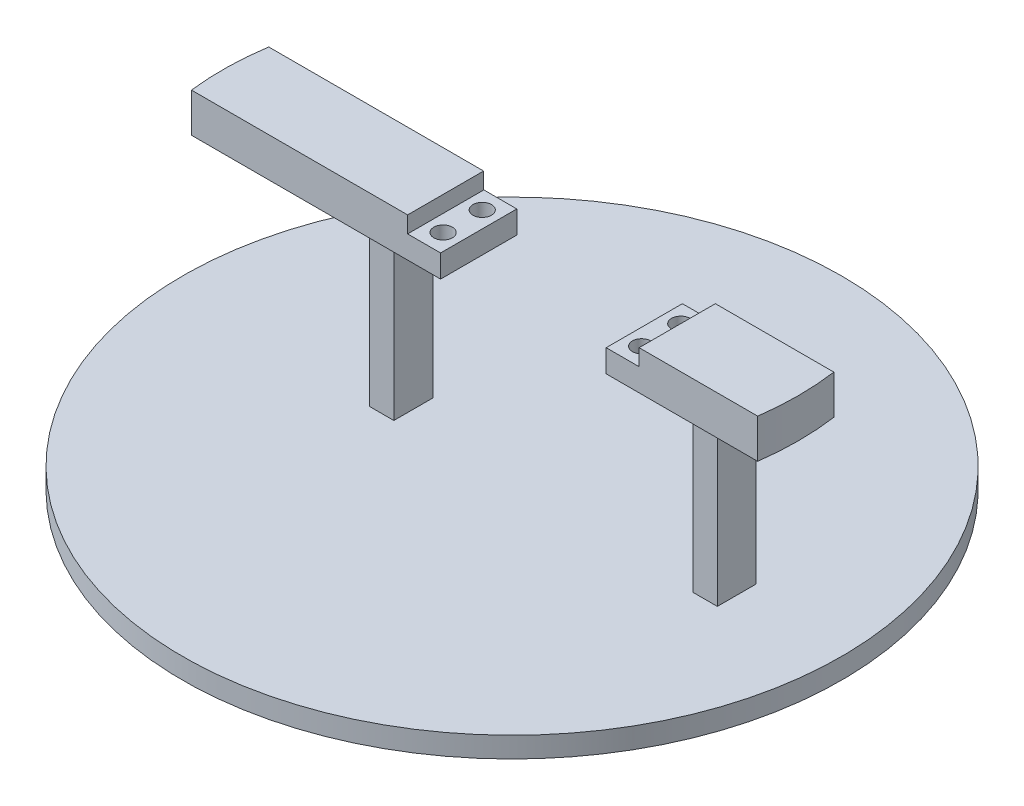
SolidWorks part; units mm, degrees
ref_plane "Front Plane" through (0, 0, 0) normal (0, 0, 1) x (1, 0, 0)
ref_plane "Top Plane" through (0, 0, 0) normal (0, 1, 0) x (1, 0, 0)
ref_plane "Right Plane" through (0, 0, 0) normal (1, 0, 0) x (0, 0, -1)
sketch "Sketch1" plane through (0, 0, 0) normal (0, 1, 0) x (1, 0, 0)
  line L0 (0, 0) -> (-8, 0) construction
  line L1 (0, 0) -> (32, 0.2728) construction
  line L2 (0, 0) -> (0, 18.5) construction
  line L3 (-8, 0) -> (-8, 18.5) construction
  line L4 (32, 0.2728) -> (32, 18.7728) construction
  line L5 (36.0049, 7.3378) -> (36.0049, 11.8378) construction
  line L6 (36.0049, 18.8378) -> (36.0049, 16.8378) construction
  line L7 (36.0049, 9.5878) -> (40.1019, 9.5878) construction
  line L8 (40.1019, 9.5878) -> (32.3835, 9.5878) construction
  line L9 (36.0049, 0.4295) -> (36.0049, 2.3378) construction
  line L10 (36.0049, 7.3378) -> (36.0049, 2.3378) construction
  line L11 (31.9989, 18.7362) -> (39.9989, 18.7362)
  line L12 (31.9989, 18.7362) -> (31.9989, 0.2362)
  line L13 (31.9989, 0.2362) -> (39.9989, 0.2362)
  line L14 (39.9989, 18.7362) -> (39.9989, 0.2362)
  line L15 (39.6049, 0.2362) -> (32.4049, 0.2362)
  line L16 (-12.0097, 7.1563) -> (-12.0097, 11.6563) construction
  line L17 (-12.0097, 18.6563) -> (-12.0097, 16.6563) construction
  line L18 (-12.0097, 9.4063) -> (-7.9127, 9.4063) construction
  line L19 (-7.9127, 9.4063) -> (-15.9127, 9.4063) construction
  line L20 (-12.0097, 0.2481) -> (-12.0097, 2.1563) construction
  line L21 (-12.0097, 7.1563) -> (-12.0097, 2.1563) construction
  line L22 (-16.0157, 18.5547) -> (-8.0157, 18.5547)
  line L23 (-16.0157, 18.5547) -> (-16.0157, 0.0547)
  line L24 (-16.0157, 0.0547) -> (-8.0157, 0.0547)
  line L25 (-8.0157, 18.5547) -> (-8.0157, 0.0547)
  line L26 (-8.4097, 0.0547) -> (-15.6097, 0.0547)
  line L27 (31.9989, 18.7362) -> (69.3989, 18.7362) construction
  line L28 (69.3989, 18.7362) -> (69.3989, 0.2362) construction
  line L29 (-8, 18.5) -> (-68.1667, 18.5) construction
  line L30 (-69, 18.5) -> (-69, 0) construction
  line L31 (54.3835, 18.7362) -> (0, 18.5) construction
  line L32 (-68.1667, 18.5) -> (-16.0157, 18.5)
  line L34 (-68.486, 0.0547) -> (-16.0157, 0.0547)
  line L35 (-16.0157, 18.5) -> (-16.0157, 0.0547)
  line L36 (39.9989, 18.7362) -> (68.7682, 18.7362)
  line L37 (39.9989, 18.7362) -> (39.9989, 0.2362)
  line L38 (39.9989, 0.2362) -> (68.7774, 0.2362)
  line L40 (0, 18.5) -> (-54.38, 18.5) construction
  line L41 (-7.9127, 9.4063) -> (-29.9127, 9.4063) construction
  line L42 (-54.38, 9.4063) -> (-54.4296, 9.6224) construction
  line L43 (-29.9127, 14.1563) -> (-29.9127, 4.6563) construction
  line L44 (32.3835, 9.5878) -> (54.3835, 9.5878) construction
  line L45 (54.3835, 9.5878) -> (54.3835, 18.7362) construction
  line L46 (-29.9127, 4.6563) -> (-23.9627, 4.6563) construction
  line L47 (54.3835, 9.5878) -> (54.3835, 4.8378) construction
  line L48 (48.437, 9.5878) -> (48.437, 4.8378) construction
  line L49 (48.437, 4.8378) -> (54.3835, 4.8378) construction
  line L50 (54.3835, 4.8378) -> (54.3835, 14.162) construction
  line L51 (54.3835, 14.162) -> (48.437, 14.162) construction
  line L52 (48.437, 14.162) -> (48.437, 9.5878) construction
  line L53 (-23.9627, 4.6563) -> (-23.9627, 14.1563) construction
  line L54 (-29.9127, 14.1563) -> (-23.9627, 14.1563) construction
  line L55 (-29.9127, 9.4063) -> (1.9096, 9.4527) construction
  line L56 (-29.9127, 4.6563) -> (-23.9627, 4.6563)
  line L57 (-29.9127, 4.6563) -> (-29.9127, 14.1563)
  line L58 (-29.9127, 14.1563) -> (-23.9627, 14.1563)
  line L59 (-23.9627, 4.6563) -> (-23.9627, 14.1563)
  line L60 (48.437, 4.8378) -> (54.3835, 4.8378)
  line L61 (48.437, 4.8378) -> (48.437, 14.162)
  line L62 (48.437, 14.162) -> (54.3835, 14.162)
  line L63 (54.3835, 4.8378) -> (54.3835, 14.162)
  circle A0 centre (36.0049, 4.8378) radius 2.25
  circle A1 centre (36.0049, 14.3378) radius 2.25
  circle A2 centre (-12.0097, 4.6563) radius 2.25
  circle A3 centre (-12.0097, 14.1563) radius 2.25
  arc A4 (-68.1667, 18.5) -> (-68.486, 0.0547) centre (-1.4696, 8.1199) ccw
  arc A6 (68.7774, 0.2362) -> (68.7682, 18.7362) centre (1.9096, 9.4527) ccw
  point P71 (-23.9627, 9.4063)
  dimension "D6" = 4.5
  dimension "D9" = 4.5
  dimension "D16" = 54.3835
  dimension "D17" = 22
  dimension "D1" = 8
  dimension "D2" = 32
  dimension "D3" = 18.5
  dimension "D4" = 18.5
  dimension "D5" = 18.5
  dimension "D7" = 18.5
  dimension "D8" = 8
  dimension "D10" = 18.5
  dimension "D11" = 8
  dimension "D12" = 37.4
  dimension "D13" = 18.5
  dimension "D14" = 61
  dimension "D15" = 18.5
  dimension "D18" = 5.9465
  dimension "D19" = 4.75
  dimension "D20" = 22
  dimension "D21" = 5.95
extrude "Boss-Extrude1" add sketch "Sketch1" along normal blind 5.5 contours L25 L22 L23 L24 A2 A3 region at (-12.0173, 0, -9.2769)
extrude "Boss-Extrude2" add sketch "Sketch1<3>" along normal blind 9.5 contours L32 A4 L34 L23 region at (-43.3357, 0, -9.2596)
sketch "Sketch1<3>" plane through (0, 0, 0) normal (0, 1, 0) x (1, 0, 0) same geometry as "Sketch1"
extrude "Boss-Extrude3" add sketch "Sketch1<4>" along normal blind 5.5 separate body contours L14 L11 L12 L13 A0 A1 region at (35.9973, 0, -9.4584)
sketch "Sketch1<4>" plane through (0, 0, 0) normal (0, 1, 0) x (1, 0, 0) same geometry as "Sketch1"
extrude "Boss-Extrude4" add sketch "Sketch1<5>" along normal blind 9.5 contours L38 A6 L36 L14 region at (54.9637, 0, -9.4841)
sketch "Sketch1<5>" plane through (0, 0, 0) normal (0, 1, 0) x (1, 0, 0) same geometry as "Sketch1"
extrude "Boss-Extrude5" add sketch "Sketch1<6>" against normal blind 45 and the other way blind 9.5 contours L58 L59 L56 L57 | L62 L63 L60 L61
sketch "Sketch1<6>" plane through (0, 0, 0) normal (0, 1, 0) x (1, 0, 0) same geometry as "Sketch1"
sketch "Sketch2" plane through (0, -45, 0) normal (0, -1, 0) x (1, 0, 0)
  line L0 (-23.9627, -4.6563) -> (-29.9127, -14.1563) construction
  line L1 (-29.9127, -14.1563) -> (-29.9127, -4.6563) construction
  line L2 (-29.9127, -4.6563) -> (-23.9627, -14.1563) construction
  line L3 (-23.9627, -14.1563) -> (-26.9377, -9.4063) construction
  line L4 (-26.9377, -9.4063) -> (51.7898, -9.4063) construction
  line L5 (51.7898, -9.4063) -> (54.3835, -4.8378) construction
  line L6 (54.3835, -4.8378) -> (48.437, -14.162) construction
  line L7 (48.437, -14.162) -> (54.3835, -14.162) construction
  line L8 (48.437, -4.8378) -> (48.437, -14.162) construction
  line L9 (48.437, -14.162) -> (51.7898, -9.4063) construction
  line L10 (51.7898, -9.4063) -> (48.437, -4.8378) construction
  line L11 (48.437, -4.8378) -> (54.3835, -14.162) construction
  line L12 (48.437, -14.162) -> (54.3835, -14.162) construction
  line L13 (-8.0157, -4.6563) -> (-8.0157, -9.3047) construction
  line L14 (-8.0157, -18.5547) -> (-8.0157, -0.0547) construction
  line L15 (-8.0157, -4.6563) -> (-0.0157, -4.6563) construction
  line L16 (-0.0157, -4.6563) -> (-0.0157, -9.4063) construction
  circle A0 centre (-0.0157, -9.4063) radius 80
  dimension "D2" = 160
  dimension "D1" = 8
extrude "Boss-Extrude6" add sketch "Sketch2" against normal blind 5
ref_plane "Plane1" through (68.7774, 0, -0.2362) normal (0.1365, 0, -0.9906) x (-0.9906, 0, -0.1365)
sketch "Sketch3" plane through (68.7774, 0, -0.2362) normal (0.1365, 0, -0.9906) x (-0.9906, 0, -0.1365)
  line L0 (93.4359, -5.0558) -> (93.4359, 0)
  line L1 (93.4359, 0) -> (87.9015, 0)
  line L2 (21.4678, 0) -> (46.3553, -39.3693) construction
  line L3 (14.5574, 0) -> (-4.0473, -39.3693) construction
  line L4 (93.4359, 0) -> (74.5305, -39.3693) construction
  line L5 (100.6332, 0) -> (128.0805, -39.3693) construction
